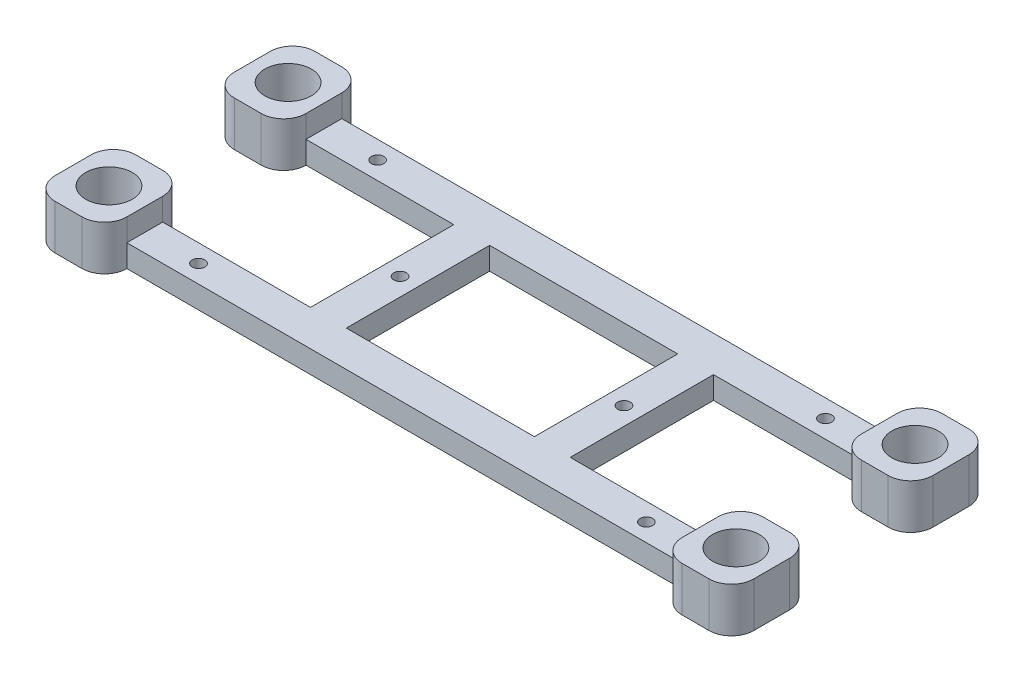
SolidWorks part; units mm, degrees
ref_plane "Front Plane" through (0, 0, 0) normal (0, 0, 1) x (1, 0, 0)
ref_plane "Top Plane" through (0, 0, 0) normal (0, 1, 0) x (1, 0, 0)
ref_plane "Right Plane" through (0, 0, 0) normal (1, 0, 0) x (0, 0, -1)
sketch "Sketch1" plane through (0, 0, 0) normal (0, 1, 0) x (1, 0, 0)
  line L0 (0, 9) -> (156, 9) construction
  line L1 (0, 0) -> (16, 0)
  line L2 (0, 0) -> (0, 18)
  line L3 (0, 18) -> (16, 18)
  line L4 (156, 0) -> (156, 18)
  line L5 (16, 18) -> (16, 0) construction
  line L6 (140, 18) -> (140, 0) construction
  line L8 (16, 13) -> (140, 13) construction
  line L9 (16, 5) -> (140, 5) construction
  line L10 (140, 18) -> (156, 18)
  line L11 (140, 0) -> (156, 0)
  line L12 (78, 21) -> (78, -4.7621) construction
  line L13 (16, 0) -> (16, 5)
  line L14 (16, 5) -> (140, 5)
  line L15 (140, 5) -> (140, 0)
  line L16 (16, 18) -> (16, 13)
  line L17 (16, 13) -> (140, 13)
  line L18 (140, 13) -> (140, 18)
  circle A0 centre (8, 9) radius 5.2
  circle A1 centre (148, 9) radius 5.2
  circle A2 centre (28, 9) radius 1.4
  circle A3 centre (128, 9) radius 1.4
  dimension "D1" = 10.4
  dimension "D2" = 10.4
  dimension "D3" = 140
  dimension "D4" = 8
  dimension "D11" = 2.8
  dimension "D12" = 20
  dimension "D5" = 8
  dimension "D6" = 9
  dimension "D7" = 8
  dimension "D8" = 4
  dimension "D9" = 8
  dimension "D10" = 8
extrude "Boss-Extrude1" add sketch "Sketch1" along normal blind 10
sketch "Sketch2" plane through (0, 0, 0) normal (0, 0, 1) x (1, 0, 0)
  line L0 (0, 5) -> (156, 5) construction
  line L1 (0, 10) -> (0, 0) construction
  line L2 (156, 10) -> (156, 0) construction
  line L7 (16, 10) -> (16, 5)
  line L8 (16, 10) -> (16, 0) construction
  line L9 (16, 5) -> (140, 5)
  line L10 (140, 10) -> (140, 0) construction
  line L11 (140, 5) -> (140, 10)
  line L12 (140, 10) -> (16, 10)
extrude "Cut-Extrude1" cut sketch "Sketch2" against normal through all
fillet "Fillet1" radius 5 8 edges at (140, 5, 0) (156, 5, 0) (156, 5, -18) (140, 5, -18) (0, 5, 0) (0, 5, -18) (16, 5, -18) (16, 5, 0)
move or copy body "Body-Move/Copy1" bodies to move or copy 102 copy yes number of copies 1 translate (0, 0, 40)
sketch "Sketch3" plane through (0, 0, 0) normal (0, 1, 0) x (1, 0, 0)
  line L0 (78, 13) -> (78, -35) construction
  line L1 (16, 13) -> (140, 13) construction
  line L2 (140, -35) -> (16, -35) construction
  line L3 (28, 9) -> (28, -31) construction
  line L4 (128, 9) -> (128, -31) construction
  line L5 (28, -11) -> (78, -11) construction
  line L6 (53, -11) -> (53, 5) construction
  line L7 (140, 5) -> (16, 5) construction
  line L9 (49, -27) -> (57, -27)
  line L10 (49, -27) -> (49, 5)
  line L11 (49, 5) -> (57, 5)
  line L12 (57, -27) -> (57, 5)
  line L13 (49, -27) -> (57, 5) construction
  line L14 (49, 5) -> (57, -27) construction
  line L15 (107, 5) -> (99, 5)
  line L16 (99, -27) -> (99, 5)
  line L17 (107, -27) -> (99, -27)
  line L18 (107, -27) -> (107, 5)
  dimension "D1" = 8
extrude "Boss-Extrude2" add sketch "Sketch3" along normal up to surface (5 mm away) up to face at (28, 5, -10.4)
sketch "Sketch4" plane through (0, 5, 0) normal (0, 1, 0) x (1, 0, 0)
  line L0 (49, -11) -> (107, -11) construction
  line L1 (49, -27) -> (49, 5) construction
  line L2 (107, 5) -> (107, -27) construction
  circle A0 centre (53, -11) radius 1.4
  circle A1 centre (103, -11) radius 1.4
  point P10 (0, 0)
  point P11 (0, 0)
  dimension "D1" = 2.8
  dimension "D2" = 2.8
  dimension "D4" = 4
  dimension "D3" = 4
extrude "Cut-Extrude2" cut sketch "Sketch4" against normal through all
